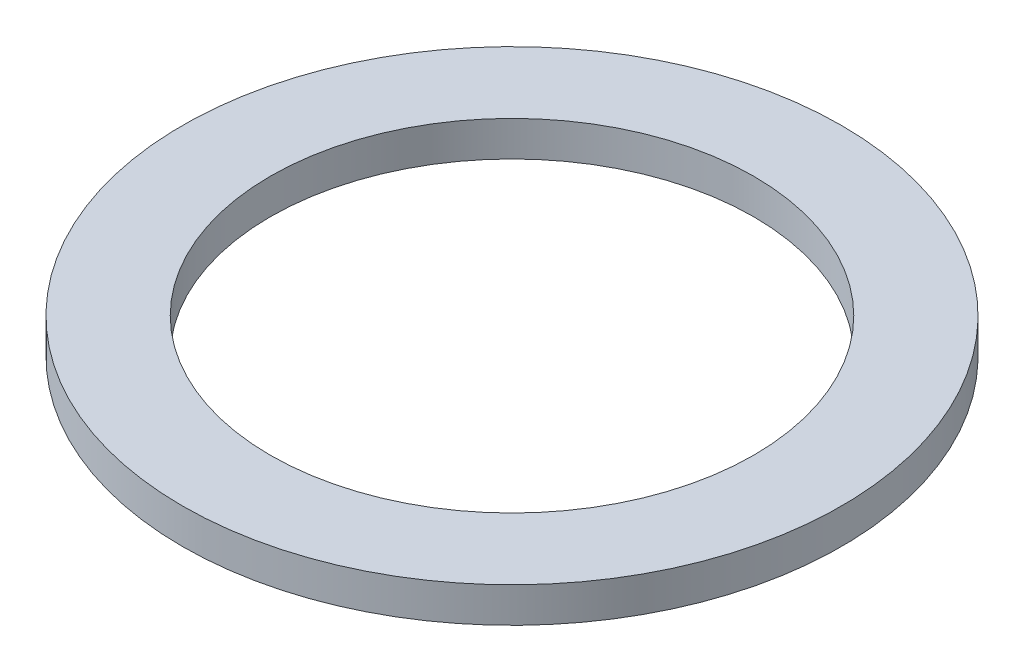
SolidWorks part; units mm, degrees
ref_plane "Front Plane" through (0, 0, 0) normal (0, 0, 1) x (1, 0, 0)
ref_plane "Top Plane" through (0, 0, 0) normal (0, 1, 0) x (1, 0, 0)
ref_plane "Right Plane" through (0, 0, 0) normal (1, 0, 0) x (0, 0, -1)
sketch "Sketch1" plane through (0, 0, 0) normal (0, 1, 0) x (1, 0, 0)
  circle A0 centre (0, 0) radius 37.5
  dimension "FLANGE_OD" = 75
extrude "Boss-Extrude1" add sketch "Sketch1" along normal blind 4
sketch "Sketch2" plane through (0, 0, 0) normal (0, 1, 0) x (1, 0, 0)
  circle A0 centre (0, 0) radius 27.5
  dimension "BORE_D" = 55
extrude "Cut-Extrude1" cut sketch "Sketch2" along normal through all
sketch "Sketch3" plane through (0, 4, 0) normal (0, 1, 0) x (1, 0, 0)
  circle A0 centre (0, 0) radius 16.6279 construction
  circle A1 centre (-16.6279, 0) radius 1.5277
  dimension "BOLT_D" = 3.0554
  dimension "BOLT_PCD" = 33.2558
extrude "Cut-Extrude2" cut sketch "Sketch3" against normal blind 3.2868 rebuild error yes
pattern_circular "CirPattern1" count 5 over 360 rebuild error yes
